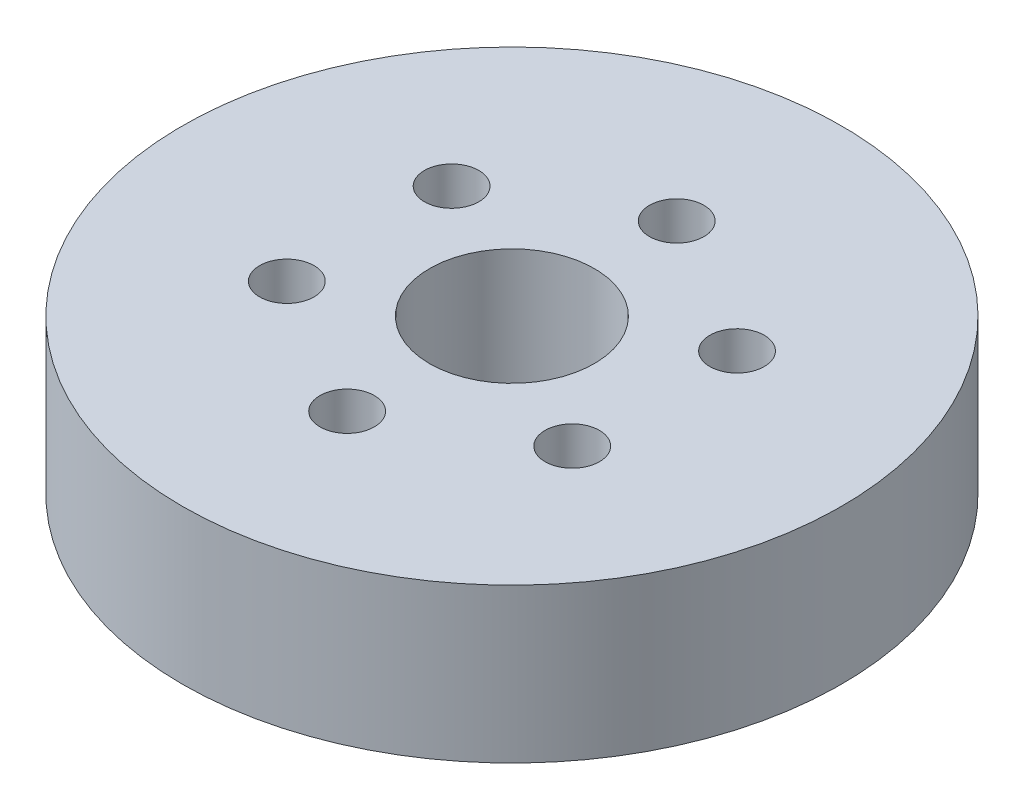
SolidWorks part; units mm, degrees
material "6061 Alloy"
ref_plane "Front Plane" through (0, 0, 0) normal (0, 0, 1) x (1, 0, 0)
ref_plane "Top Plane" through (0, 0, 0) normal (0, 1, 0) x (1, 0, 0)
ref_plane "Right Plane" through (0, 0, 0) normal (1, 0, 0) x (0, 0, -1)
ref_axis "X Axis" through (-88.99, 0, 0) along (1, 0, 0)
ref_axis "Y Axiz" through (0, 0, 55) along (0, 0, -1)
ref_axis "Z Axis" through (0, 55, 0) along (0, -1, 0)
sketch "Sketch1" plane through (0, 0, 0) normal (0, 1, 0) x (1, 0, 0)
  line L0 (0, 0) -> (0, 10) construction
  circle A0 centre (0, 0) radius 20
  circle A1 centre (0, 10) radius 1
  circle A2 centre (8.6603, 5) radius 1
  circle A3 centre (8.6603, -5) radius 1
  circle A4 centre (0, -10) radius 1
  circle A5 centre (-8.6603, -5) radius 1
  circle A6 centre (-8.6603, 5) radius 1
  circle A7 centre (0, 0) radius 5
  point P17 (0, 0)
  dimension "D1" = 10
  dimension "D2" = 2
  dimension "D4" = 40
  dimension "D5" = 10
  dimension "D3" = 6
extrude "Boss-Extrude1" add sketch "Sketch1" along normal blind 9.35
hole_wizard "M4x0.7 Tapped Hole1" positions "3DSketch1" profile "Sketch2" tap size "M4x0.7" standard "ANSI Metric" end condition through all
sketch3d "3DSketch1"
  line L0 (-8.6603, 9.35, 5) -> (-8.6603, 0, 5) construction
  line L1 (0, 9.35, 10) -> (0, 0, 10) construction
  line L2 (8.6603, 9.35, 5) -> (8.6603, 0, 5) construction
  line L3 (8.6603, 9.35, -5) -> (8.6603, 0, -5) construction
  line L4 (0, 9.35, -10) -> (0, 0, -10) construction
  line L5 (-8.6603, 9.35, -5) -> (-8.6603, 0, -5) construction
  point P0 (-8.6603, 0, 5)
  point P4 (0, 0, 10)
  point P8 (8.6603, 0, 5)
  point P12 (8.6603, 0, -5)
  point P16 (0, 0, -10)
  point P20 (-8.6603, 0, -5)
sketch "Sketch2" plane through (-8.6603, 0, 5) normal (1, 0, 0) x (0, 0, -1)
  line L0 (0, 0) -> (0, 9.35)
  line L1 (0, 9.35) -> (1.65, 9.35)
  line L2 (1.65, 9.35) -> (1.65, 0)
  line L5 (1.65, 0) -> (0, 0)
  line L11 (0, -6.35) -> (0, 107.95) construction
  dimension "Thru Tap Drill Dia." = 3.3
  dimension "Thru Tap Drill Depth" = 9.35
cosmetic thread "Hole Thread1" parameters "D2"=4
cosmetic thread "Hole Thread2" parameters "D2"=4
cosmetic thread "Hole Thread3" parameters "D2"=4
cosmetic thread "Hole Thread4" parameters "D2"=4
cosmetic thread "Hole Thread5" parameters "D2"=4
cosmetic thread "Hole Thread6" parameters "D2"=4
